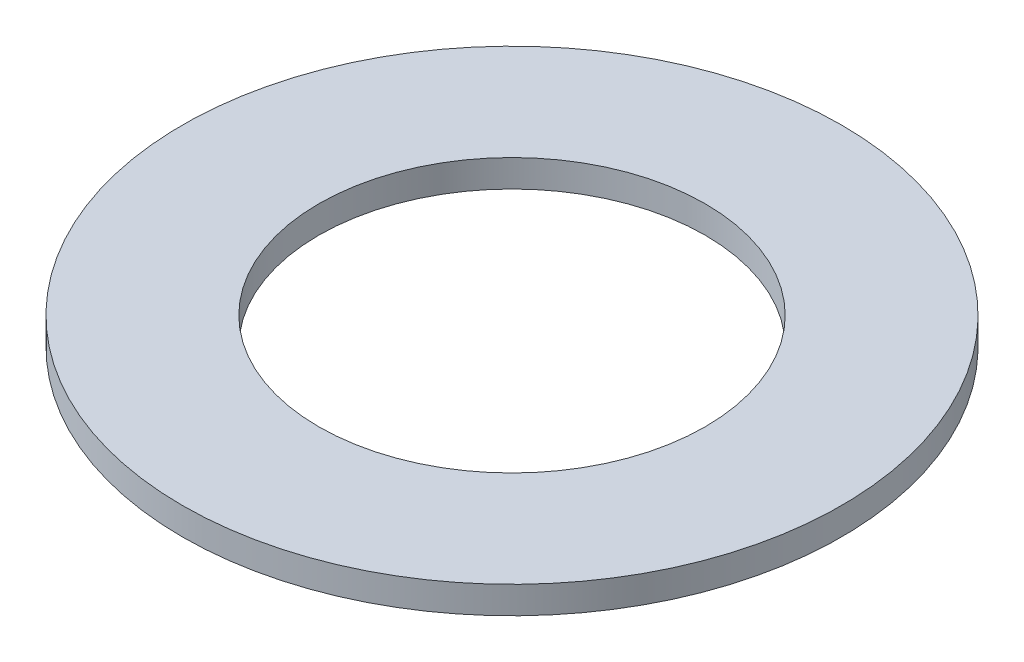
SolidWorks part; units mm, degrees
ref_plane "Front Plane" through (0, 0, 0) normal (0, 0, 1) x (1, 0, 0)
ref_plane "Top Plane" through (0, 0, 0) normal (0, 1, 0) x (1, 0, 0)
ref_plane "Right Plane" through (0, 0, 0) normal (1, 0, 0) x (0, 0, -1)
sketch "Sketch1" plane through (0, 0, 0) normal (0, 1, 0) x (1, 0, 0)
  circle A0 centre (0, 0) radius 72.5
  dimension "FLANGE_OD" = 145
extrude "Boss-Extrude1" add sketch "Sketch1" along normal blind 6
sketch "Sketch2" plane through (0, 0, 0) normal (0, 1, 0) x (1, 0, 0)
  circle A0 centre (0, 0) radius 42.5
  dimension "BORE_D" = 85
extrude "Cut-Extrude1" cut sketch "Sketch2" along normal through all
sketch "Sketch3" plane through (0, 6, 0) normal (0, 1, 0) x (1, 0, 0)
  circle A0 centre (0, 0) radius 28.6934 construction
  circle A1 centre (-28.6934, 0) radius 2.1643
  dimension "BOLT_D" = 4.3287
  dimension "BOLT_PCD" = 57.3868
extrude "Cut-Extrude2" cut sketch "Sketch3" against normal blind 5.7177 rebuild error yes
pattern_circular "CirPattern1" count 5 over 360 rebuild error yes
